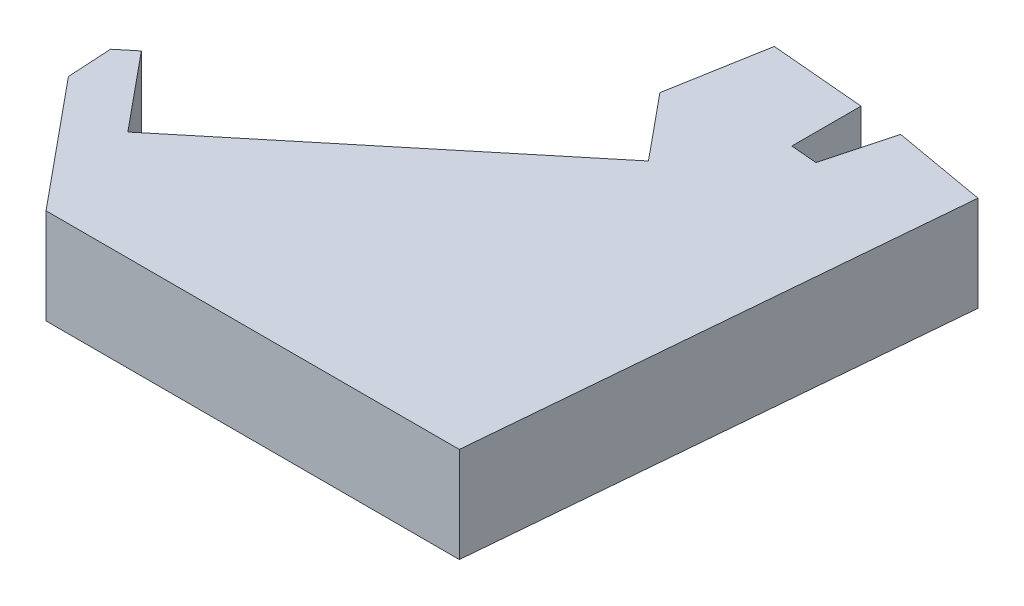
SolidWorks part; units mm, degrees
ref_plane "前视基准面" through (0, 0, 0) normal (0, 0, 1) x (1, 0, 0)
ref_plane "上视基准面" through (0, 0, 0) normal (0, 1, 0) x (1, 0, 0)
ref_plane "右视基准面" through (0, 0, 0) normal (1, 0, 0) x (0, 0, -1)
sketch "草图1" plane through (0, 0, 0) normal (0, 1, 0) x (1, 0, 0)
  line L0 (0, 0) -> (78, 0)
  line L1 (78, 0) -> (85.874, 90)
  line L2 (85.874, 90) -> (68.1474, 93.1257)
  line L3 (68.1474, 93.1257) -> (64.7699, 80.5207)
  line L4 (64.7699, 80.5207) -> (59.789, 80.9564)
  line L5 (59.789, 80.9564) -> (59.789, 94.0061)
  line L6 (59.789, 94.0061) -> (41.8575, 95.5749)
  line L7 (41.8575, 95.5749) -> (38.6208, 77.2186)
  line L9 (-5.1543, 20.5926) -> (48.7062, 64.9811)
  line L10 (48.7062, 64.9811) -> (38.6208, 77.2186)
  line L15 (-17.1281, 35.1214) -> (-20.3134, 32.4963)
  line L16 (-20.3134, 32.4963) -> (-19.8335, 24.0658)
  line L17 (-17.1281, 35.1214) -> (-5.1543, 20.5926)
  line L18 (0, 0) -> (-19.8335, 24.0658)
  point P11 (-19.8335, 32.3302)
  point P12 (-20.3134, 32.4963)
  dimension "D1" = 18
  dimension "D2" = 18
  dimension "D4" = 95
  dimension "D5" = 95
  dimension "D7" = 90
  dimension "D3" = 5
  dimension "D8" = 78
  dimension "D9" = 95
  dimension "D10" = 95
  dimension "D11" = 95
  dimension "D12" = 95
  dimension "D6" = 13
  dimension "D13" = 13
  dimension "D14" = 100
extrude "凸台-拉伸1" add sketch "草图1" along normal blind 18
ref_point "点1"
ref_point "点2"
equation "\"sz_jd\"= 95'指根角度"
equation "\"sz_zj\"= 16'食指直径"
equation "\"zz_zj\"= 16'中指直径"
equation "\"wz_zj\"= 16'无名指直径"
equation "\"xz_zj\"= 16'小指直径"
equation "\"zg_cd\"= 13'指根长度"
equation "\"D1@草图1\"=\"zz_zj\" +2"
equation "\"D2@草图1\"=\"zz_zj\" +2"
equation "\"sz_zc\"= 90'掌长"
equation "\"D7@草图1\"= \"sz_zc\""
equation "\"sz_zdc\"= 78'掌底"
equation "\"sz_zdjd\"= 95'掌底拇指边角度"
equation "\"D8@草图1\"=\"sz_zdc\""
equation "\"D9@草图1\"=\"sz_zdjd\""
equation "\"D10@草图1\"=\"sz_jd\""
equation "\"D11@草图1\"=\"sz_jd\""
equation "\"D12@草图1\"=\"sz_jd\""
equation "\"D6@草图1\"=\"zg_cd\""
equation "\"D13@草图1\"=\"zg_cd\""
equation "\"sz_szjd\"= 100'食指中指角度"
equation "\"D14@草图1\"=\"sz_szjd\""
equation "\"D1@凸台-拉伸1\"=\"sz_zj\" +2"
